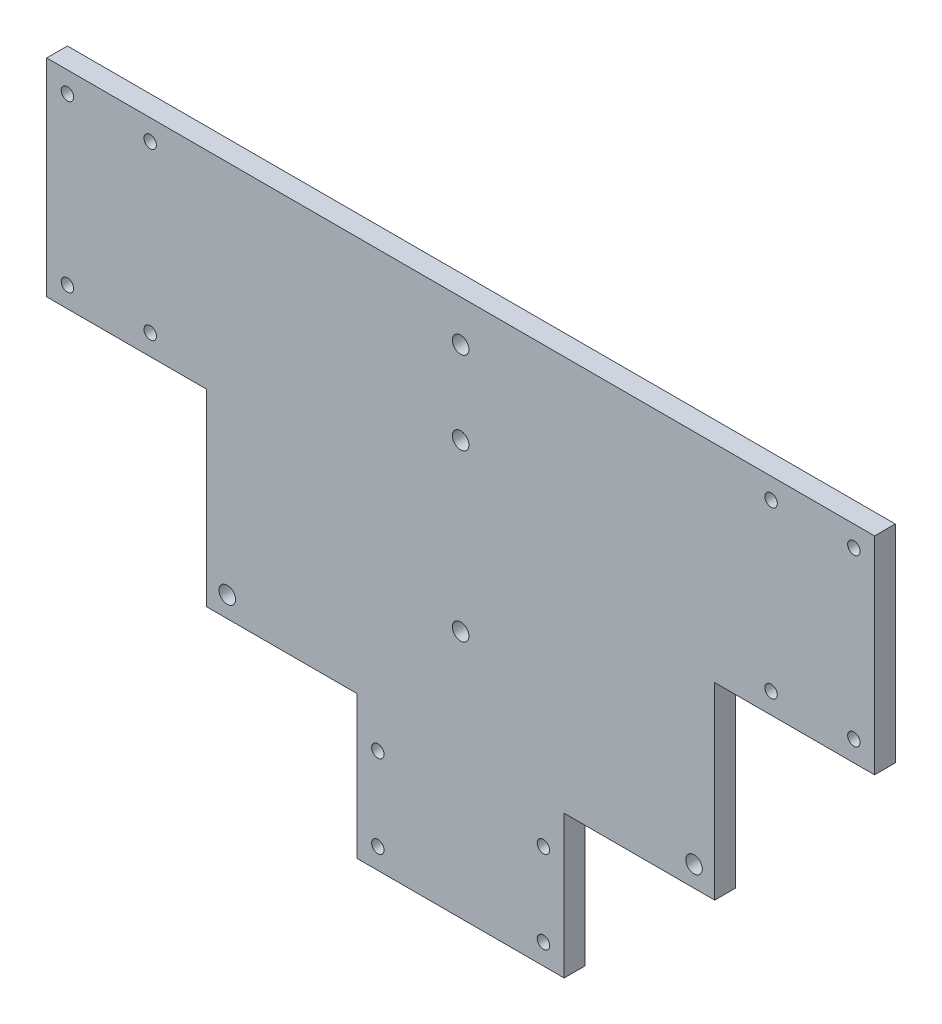
SolidWorks part; units mm, degrees
ref_plane "Plan de face" through (0, 0, 0) normal (0, 0, 1) x (1, 0, 0)
ref_plane "Plan de dessus" through (0, 0, 0) normal (0, 1, 0) x (1, 0, 0)
ref_plane "Plan de droite" through (0, 0, 0) normal (1, 0, 0) x (0, 0, -1)
sketch "Esquisse1" plane through (0, 0, 0) normal (0, 0, 1) x (1, 0, 0)
  line L0 (-25, 0) -> (25, 0) construction
  line L1 (0, 50) -> (-100, 50)
  line L2 (25, -80) -> (25, -45.5212)
  line L3 (-70, 50) -> (-70, 0) construction
  line L4 (25, -80) -> (-25, -80)
  line L5 (-25, -50) -> (25, -50) construction
  line L6 (-25, -65) -> (25, -65) construction
  line L7 (-25, -80) -> (-25, -45.5212)
  line L8 (0, 50) -> (0, -80) construction
  line L9 (-85, 50) -> (-85, 0) construction
  line L10 (0, 50) -> (100, 50)
  line L11 (100, 50) -> (100, 0)
  line L12 (100, 0) -> (61.3816, 0)
  line L13 (-100, 50) -> (-100, 0)
  line L14 (-100, 0) -> (-61.3816, 0)
  line L15 (61.3816, 0) -> (25, 0) construction
  line L16 (-100, 25) -> (-70, 25) construction
  line L17 (-25, -45.5212) -> (-25, 0) construction
  line L18 (-61.3816, 0) -> (-61.3816, -45.5212)
  line L19 (-61.3816, -45.5212) -> (-25, -45.5212)
  line L20 (0, -20) -> (-25, -20) construction
  line L21 (25, -45.5212) -> (25, 0) construction
  line L22 (61.3816, 0) -> (61.3816, -45.5212)
  line L23 (61.3816, -45.5212) -> (25, -45.5212)
  line L24 (0, -20) -> (-56.3816, -40.5212) construction
  circle A0 centre (0, 20) radius 2
  circle A1 centre (0, -20) radius 2
  circle A2 centre (0, 40) radius 2
  circle A3 centre (-20, -55) radius 1.5
  circle A4 centre (20, -55) radius 1.5
  circle A5 centre (20, -75) radius 1.5
  circle A6 centre (-20, -75) radius 1.5
  circle A7 centre (-95, 45) radius 1.5
  circle A8 centre (-75, 45) radius 1.5
  circle A9 centre (-75, 5) radius 1.5
  circle A10 centre (-95, 5) radius 1.5
  circle A11 centre (75, 5) radius 1.5
  circle A12 centre (95, 5) radius 1.5
  circle A13 centre (75, 45) radius 1.5
  circle A14 centre (95, 45) radius 1.5
  circle A15 centre (56.3816, -40.5212) radius 2
  circle A17 centre (-56.3816, -40.5212) radius 2
  point P0 (0, 0)
  point P2 (0, 0)
  dimension "D3" = 4
  dimension "D4" = 4
  dimension "D5" = 20
  dimension "D7" = 4
  dimension "D13" = 3
  dimension "D14" = 20
  dimension "D19" = 3
  dimension "D20" = 10
  dimension "D21" = 20
  dimension "D22" = 5
  dimension "D23" = 5
  dimension "D24" = 60
  dimension "D25" = 20
  dimension "D26" = 4
  dimension "D27" = 25
  dimension "D6" = 20
  dimension "D8" = 40
  dimension "D9" = 80
  dimension "D10" = 30
  dimension "D11" = 30
  dimension "D12" = 15
  dimension "D15" = 10
  dimension "D16" = 100
  dimension "D17" = 50
  dimension "D18" = 15
extrude "Boss.-Extru.1" add sketch "Esquisse1" along normal blind 5
